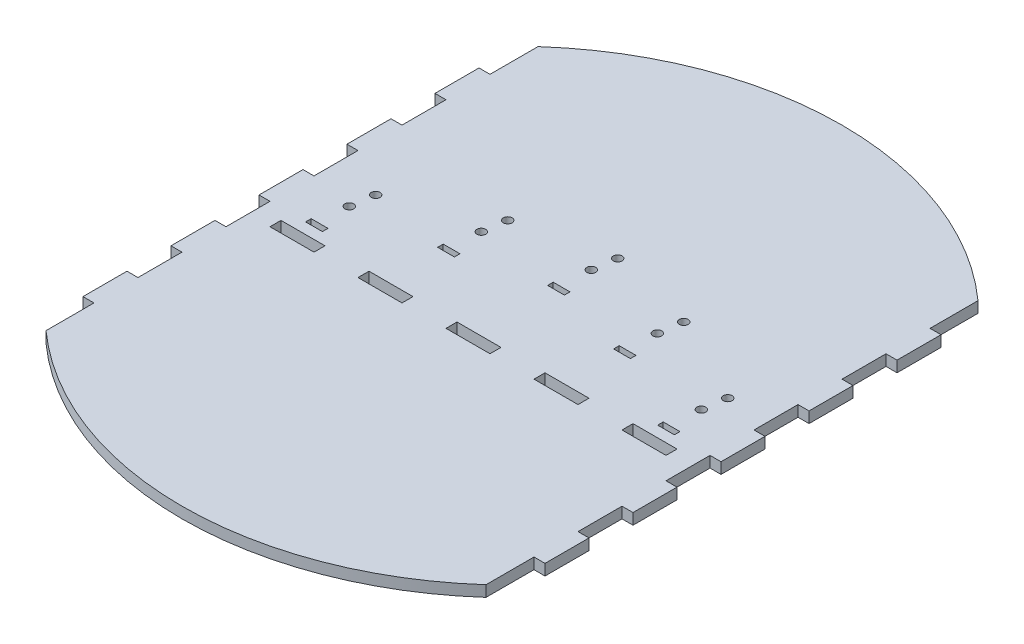
SolidWorks part; units mm, degrees
ref_plane "Přední rovina" through (0, 0, 0) normal (0, 0, 1) x (1, 0, 0)
ref_plane "Horní rovina" through (0, 0, 0) normal (0, 1, 0) x (1, 0, 0)
ref_plane "Pravá rovina" through (0, 0, 0) normal (1, 0, 0) x (0, 0, -1)
sketch "Skica1" plane through (0, 0, 0) normal (0, 1, 0) x (1, 0, 0)
  line L0 (-150, 0) -> (150, 0)
  line L5 (-200, 111.8034) -> (-100, 111.8034)
  line L6 (-200, 111.8034) -> (-200, -111.8034)
  line L7 (-200, -111.8034) -> (-100, -111.8034)
  line L8 (-100, 111.8034) -> (-100, -111.8034)
  line L9 (-200, 111.8034) -> (-100, -111.8034) construction
  line L10 (-200, -111.8034) -> (-100, 111.8034) construction
  line L15 (200, -111.8034) -> (100, -111.8034)
  line L16 (100, 111.8034) -> (100, -111.8034)
  line L17 (-100, -90) -> (-105, -90)
  line L18 (-100, -90) -> (-100, -70)
  line L19 (-100, -70) -> (-105, -70)
  line L20 (-105, -90) -> (-105, -70)
  line L21 (-100, -50) -> (-105, -50)
  line L22 (-100, -50) -> (-100, -30)
  line L23 (-100, -30) -> (-105, -30)
  line L24 (-105, -50) -> (-105, -30)
  line L25 (0, -150) -> (0, 150)
  line L26 (-100, 30) -> (-105, 30)
  line L27 (-105, 50) -> (-105, 30)
  line L28 (-100, 50) -> (-105, 50)
  line L29 (-100, 50) -> (-100, 30)
  line L30 (-100, 70) -> (-105, 70)
  line L31 (-105, 90) -> (-105, 70)
  line L32 (-100, 90) -> (-105, 90)
  line L33 (-100, 90) -> (-100, 70)
  line L34 (200, 111.8034) -> (100, 111.8034)
  line L35 (200, 111.8034) -> (200, -111.8034)
  line L36 (100, 90) -> (100, 70)
  line L37 (100, 90) -> (105, 90)
  line L38 (105, 90) -> (105, 70)
  line L39 (100, 70) -> (105, 70)
  line L40 (100, 50) -> (100, 30)
  line L41 (100, 50) -> (105, 50)
  line L42 (105, 50) -> (105, 30)
  line L43 (100, 30) -> (105, 30)
  line L44 (100, -30) -> (105, -30)
  line L45 (105, -50) -> (105, -30)
  line L46 (100, -50) -> (105, -50)
  line L47 (100, -50) -> (100, -30)
  line L48 (100, -70) -> (105, -70)
  line L49 (105, -90) -> (105, -70)
  line L50 (100, -90) -> (105, -90)
  line L51 (100, -90) -> (100, -70)
  line L52 (-3.81, 22.54) -> (3.81, 22.54)
  line L53 (-83.81, -10) -> (-76.19, -10)
  line L54 (-83.81, -10) -> (-83.81, -7.46)
  line L55 (-83.81, -7.46) -> (-76.19, -7.46)
  line L56 (-76.19, -10) -> (-76.19, -7.46)
  line L57 (-3.81, 22.54) -> (-3.81, 20)
  line L58 (-3.81, 20) -> (3.81, 20)
  line L59 (3.81, 22.54) -> (3.81, 20)
  line L60 (-43.81, 10) -> (-36.19, 10)
  line L61 (-43.81, 10) -> (-43.81, 12.54)
  line L62 (-43.81, 12.54) -> (-36.19, 12.54)
  line L63 (-36.19, 10) -> (-36.19, 12.54)
  line L64 (43.81, 10) -> (43.81, 12.54)
  line L65 (43.81, 12.54) -> (36.19, 12.54)
  line L66 (36.19, 10) -> (36.19, 12.54)
  line L67 (43.81, 10) -> (36.19, 10)
  line L68 (83.81, -7.46) -> (76.19, -7.46)
  line L69 (76.19, -10) -> (76.19, -7.46)
  line L70 (83.81, -10) -> (76.19, -10)
  line L71 (83.81, -10) -> (83.81, -7.46)
  line L72 (100, 10) -> (105, 10)
  line L73 (-100, -10) -> (-105, -10)
  line L74 (-100, -10) -> (-100, 10)
  line L75 (-100, 10) -> (-105, 10)
  line L76 (-105, -10) -> (-105, 10)
  line L77 (105, -10) -> (105, 10)
  line L78 (100, -10) -> (105, -10)
  line L79 (100, -10) -> (100, 10)
  line L80 (-40, 12.54) -> (-40, 26.04)
  line L81 (-80, -7.46) -> (-80, 6.04)
  line L82 (40, 12.54) -> (40, 26.04)
  line L83 (80, -7.46) -> (80, 6.04)
  line L84 (-100, -15) -> (100, -15)
  line L85 (50, -20) -> (30, -20)
  line L86 (-90, -15) -> (-70, -15)
  line L87 (-90, -15) -> (-90, -20)
  line L88 (-90, -20) -> (-70, -20)
  line L89 (-70, -15) -> (-70, -20)
  line L90 (-50, -15) -> (-30, -15)
  line L91 (-50, -15) -> (-50, -20)
  line L92 (-50, -20) -> (-30, -20)
  line L93 (-30, -15) -> (-30, -20)
  line L94 (-10, -15) -> (10, -15)
  line L95 (-10, -15) -> (-10, -20)
  line L96 (-10, -20) -> (10, -20)
  line L97 (10, -15) -> (10, -20)
  line L98 (30, -15) -> (30, -20)
  line L99 (50, -15) -> (30, -15)
  line L100 (50, -15) -> (50, -20)
  line L101 (90, -20) -> (70, -20)
  line L102 (70, -15) -> (70, -20)
  line L103 (90, -15) -> (70, -15)
  line L104 (90, -15) -> (90, -20)
  circle A0 centre (0, 0) radius 150
  circle A1 centre (0, 36.04) radius 2
  circle A2 centre (1.5, 46.54) radius 2
  circle A3 centre (80, 6.04) radius 2
  circle A4 centre (40, 26.04) radius 2
  circle A5 centre (41.5, 36.54) radius 2
  circle A6 centre (81.5, 16.54) radius 2
  circle A7 centre (-40, 26.04) radius 2
  circle A8 centre (-38.5, 36.54) radius 2
  circle A9 centre (-80, 6.04) radius 2
  circle A10 centre (-78.5, 16.54) radius 2
  point P2 (-150, 0)
  point P8 (150, 0)
  point P17 (-102.5, -90)
  point P50 (-76.19, -8.73)
  point P64 (-80, -7.46)
  point P71 (-40, 12.54)
  dimension "D1" = 300
  dimension "D26" = 4
  dimension "D28" = 4
  dimension "D31" = 4
  dimension "D32" = 4
  dimension "D35" = 4
  dimension "D36" = 4
  dimension "D37" = 4
  dimension "D38" = 4
  dimension "D39" = 4
  dimension "D40" = 4
  dimension "D3" = 5
  dimension "D4" = 20
  dimension "D5" = 20
  dimension "D6" = 5
  dimension "D7" = 20
  dimension "D8" = 30
  dimension "D9" = 2.54
  dimension "D10" = 7.62
  dimension "D11" = 7.62
  dimension "D12" = 2.54
  dimension "D13" = 3.81
  dimension "D14" = 80
  dimension "D15" = 7.62
  dimension "D16" = 2.54
  dimension "D17" = 40
  dimension "D18" = 20
  dimension "D19" = 10
  dimension "D20" = 10
  dimension "D21" = 10
  dimension "D22" = 20
  dimension "D23" = 5
  dimension "D24" = 50
  dimension "D25" = 90
  dimension "D27" = 13.5
  dimension "D29" = 24
  dimension "D30" = 1.5
  dimension "D33" = 13.5
  dimension "D34" = 13.5
  dimension "D41" = 1.5
  dimension "D42" = 24
  dimension "D43" = 1.5
  dimension "D44" = 24
  dimension "D45" = 13.5
  dimension "D46" = 13.5
  dimension "D47" = 1.5
  dimension "D48" = 24
  dimension "D49" = 24
  dimension "D50" = 1.5
  dimension "D51" = 200
  dimension "D52" = 15
  dimension "D53" = 20
  dimension "D54" = 20
  dimension "D55" = 20
  dimension "D56" = 10
  dimension "D57" = 20
  dimension "D58" = 20
  dimension "D59" = 5
extrude "Přidat vysunutím1" add sketch "Skica1" along normal blind 5 contours L8 A0 L25 L96 L95 L84 L93 L92 L91 L89 L88 L87 | L25 A0 L16 L84 L104 L101 L102 L100 L85 L98 L97 L96 | A3 L0 L16 A0 L25 A2 A1 L52 L59 L58 A6 A5 A4 L65 L64 L67 L66 | A9 L0 L25 L58 L57 L52 A1 A2 A0 L8 A10 A8 A7 L62 L63 L60 L61 | L25 L84 L16 L0 L68 L71 L70 L69 | L8 L84 L25 L0 L55 L56 L53 L54 | L8 L32 L31 L30 | L76 L73 L8 L0 | L76 L0 L8 L75 | L20 L17 L8 L19 | L27 L26 L29 L28 | L24 L23 L22 L21 | L38 L39 L36 L37 | L42 L43 L40 L41 | L77 L72 L79 L78 | L45 L44 L47 L46 | L49 L48 L51 L50 region at (-102.5, 0, -5) region at (-102.5, 0, 5) region at (-47.7919, 0, -69.7559) region at (-47.4623, 0, 78.2356) region at (-49.6078, 0, 7.4839) region at (-102.5, 0, -80) region at (47.8225, 0, -69.7741) region at (-102.5, 0, 80) region at (47.4623, 0, 78.2356) region at (49.6078, 0, 7.4839)
